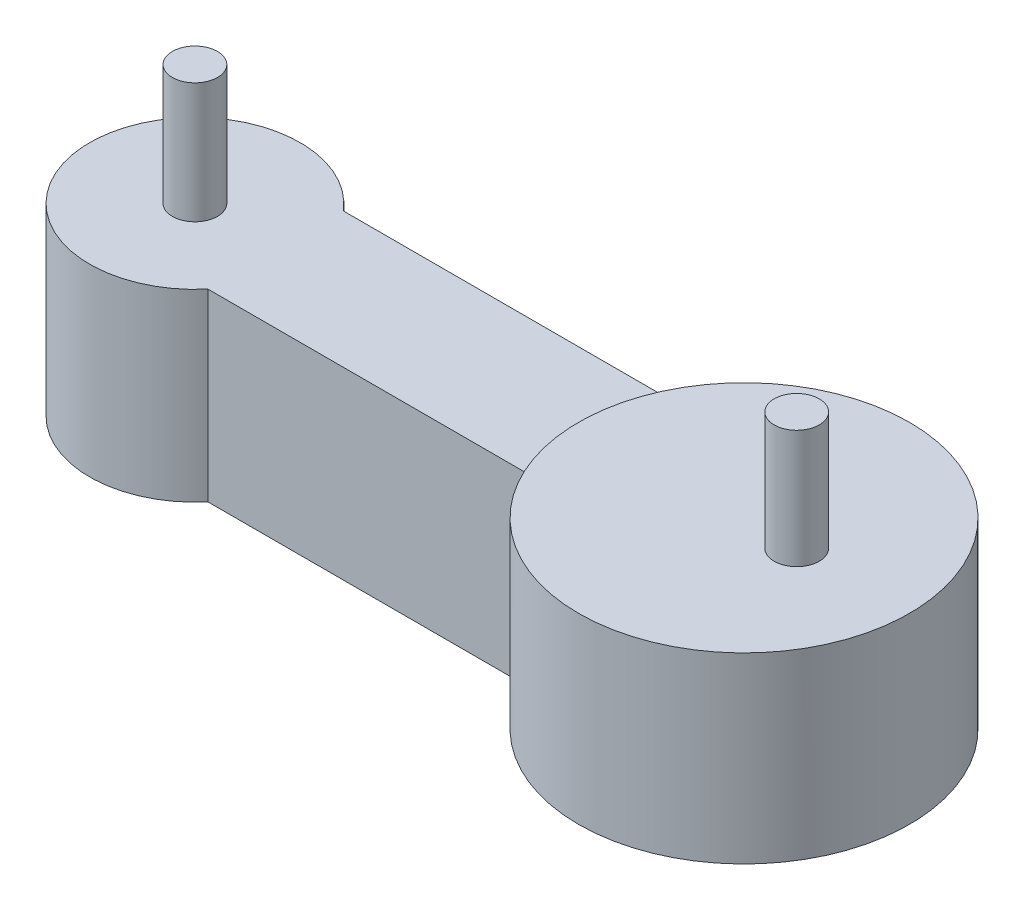
SolidWorks part; units mm, degrees
ref_plane "Front Plane" through (0, 0, 0) normal (0, 0, 1) x (1, 0, 0)
ref_plane "Top Plane" through (0, 0, 0) normal (0, 1, 0) x (1, 0, 0)
ref_plane "Right Plane" through (0, 0, 0) normal (1, 0, 0) x (0, 0, -1)
sketch "Sketch1" plane through (0, 0, 0) normal (0, 1, 0) x (1, 0, 0)
  line L0 (101.7992, 28.575) -> (-92.9519, 28.575)
  line L3 (-92.9519, -28.575) -> (101.7992, -28.575)
  arc A0 (101.7992, -28.575) -> (101.7992, 28.575) centre (127, 0) ccw
  arc A1 (-92.9519, -28.575) -> (-92.9519, 28.575) centre (-127, 0) cw
  dimension "D4" = 38.1
  dimension "D6" = 44.45
  dimension "D1" = 57.15
  dimension "D2" = 28.575
  dimension "D3" = 127
  dimension "D5" = 127
extrude "Boss-Extrude1" add sketch "Sketch1" along normal blind 1.5875
sketch "Sketch2" plane through (0, 1.5875, 0) normal (0, 1, 0) x (1, 0, 0)
  circle A0 centre (-127, 0) radius 9.525
  circle A1 centre (127, 0) radius 9.525
  dimension "D1" = 19.05
  dimension "D2" = 19.05
extrude "Boss-Extrude2" add sketch "Sketch2" along normal blind 127 contours A0
sketch "Sketch4" plane through (0, 1.5875, 0) normal (0, 1, 0) x (1, 0, 0)
  circle A0 centre (127, 0) radius 9.525
  dimension "D1" = 19.05
extrude "Boss-Extrude3" add sketch "Sketch4" along normal blind 127 and the other way blind 28.575
ref_plane "Plane1" through (0, 76.2, 0) normal (0, 1, 0) x (1, 0, 0)
sketch "Sketch5" plane through (0, 76.2, 0) normal (0, 1, 0) x (1, 0, 0)
  line L0 (-85.5662, 0) -> (85.5662, 0) construction
  circle A0 centre (127, 0) radius 9.525 construction
  circle A1 centre (127, 0) radius 9.525 construction
  circle A4 centre (104.775, 0) radius 69.85
  circle A5 centre (104.775, 0) radius 63.5
  point P6 (0, 0)
  point P9 (0, 0)
  dimension "D1" = 139.7
  dimension "D2" = 22.225
  dimension "D3" = 127
extrude "Boss-Extrude4" add sketch "Sketch5" against normal up to surface (74.6125 mm away) up to face at (127, 1.5875, -9.525)
sketch "Sketch6" plane through (0, 76.2, 0) normal (0, 1, 0) x (1, 0, 0)
  circle A0 centre (104.775, 0) radius 69.85 construction
  circle A4 centre (104.775, 0) radius 69.85
  point P0 (104.775, 0)
extrude "Boss-Extrude5" add sketch "Sketch6" along normal blind 2.54
sketch "Sketch10" plane through (0, 0, 0) normal (0, -1, 0) x (1, 0, 0)
  line L2 (-92.9519, -28.575) -> (101.7992, -28.575)
  line L3 (101.7992, 28.575) -> (-92.9519, 28.575)
  line L4 (48.0677, -28.575) -> (101.7992, -28.575)
  line L5 (101.7992, 28.575) -> (48.0677, 28.575)
  arc A2 (-92.9519, 28.575) -> (-92.9519, -28.575) centre (-127, 0) ccw
  arc A3 (101.7992, -28.575) -> (101.7992, 28.575) centre (127, 0) ccw
  arc A5 (101.7992, -28.575) -> (101.7992, 28.575) centre (127, 0) ccw
  circle A6 centre (127, 0) radius 9.525 construction
  circle A7 centre (127, 0) radius 9.525
  arc A8 (48.0677, 28.575) -> (48.0677, -28.575) centre (104.775, 0) ccw construction
  arc A9 (48.0677, 28.575) -> (48.0677, -28.575) centre (104.775, 0) ccw
  point P5 (52.0317, -28.575)
  point P13 (50.447, 28.575)
  dimension "D1" = 0
extrude "Cut-Extrude3" cut sketch "Sketch10" against normal up to next
ref_plane "Plane2" through (0, 1.5875, 0) normal (0, -1, 0) x (-1, 0, 0)
sketch "Sketch11" plane through (0, 1.5875, 0) normal (0, -1, 0) x (-1, 0, 0)
  circle A0 centre (-127, 0) radius 9.525 construction
  circle A1 centre (-127, 0) radius 9.525
  circle A2 centre (-127, 0) radius 31.75
  dimension "D1" = 63.5
extrude "Boss-Extrude6" add sketch "Sketch11" along normal blind 1.5875
sketch "Sketch13" plane through (0, 1.5875, 0) normal (0, 1, 0) x (1, 0, 0)
  line L0 (-92.9519, -28.575) -> (41.0373, -28.575) construction
  line L1 (41.0373, 28.575) -> (-92.9519, 28.575) construction
  line L2 (-92.9519, -28.575) -> (41.0373, -28.575)
  line L3 (41.0373, 28.575) -> (-92.9519, 28.575)
  line L6 (-94.1575, -26.035) -> (37.2288, -26.035)
  line L7 (37.2288, 26.035) -> (-94.1575, 26.035)
  arc A1 (-92.9519, 28.575) -> (-92.9519, -28.575) centre (-127, 0) ccw construction
  arc A3 (-92.9519, 28.575) -> (-92.9519, -28.575) centre (-127, 0) ccw
  arc A6 (-94.1575, 26.035) -> (-94.1575, -26.035) centre (-127, 0) ccw
  arc A7 (41.0373, 28.575) -> (41.0373, -28.575) centre (104.775, 0) ccw construction
  arc A8 (41.0373, 28.575) -> (41.0373, -28.575) centre (104.775, 0) ccw
  arc A9 (37.2288, 26.035) -> (37.2288, -26.035) centre (104.775, 0) ccw
  dimension "D1" = 2.54
extrude "Boss-Extrude7" add sketch "Sketch13" along normal blind 76.2
sketch "Sketch14" plane through (0, 77.7875, 0) normal (0, 1, 0) x (1, 0, 0)
  line L4 (-94.1575, -26.035) -> (37.2288, -26.035) construction
  line L5 (37.2288, 26.035) -> (-94.1575, 26.035) construction
  line L6 (-94.1575, -26.035) -> (37.2288, -26.035)
  line L7 (37.2288, 26.035) -> (-94.1575, 26.035)
  arc A5 (37.2288, 26.035) -> (37.2288, -26.035) centre (104.775, 0) ccw construction
  arc A6 (-94.1575, 26.035) -> (-94.1575, -26.035) centre (-127, 0) ccw construction
  arc A7 (37.2288, 26.035) -> (37.2288, -26.035) centre (104.775, 0) ccw
  arc A8 (-94.1575, 26.035) -> (-94.1575, -26.035) centre (-127, 0) ccw
extrude "Boss-Extrude8" add sketch "Sketch14" against normal blind 1.5875
